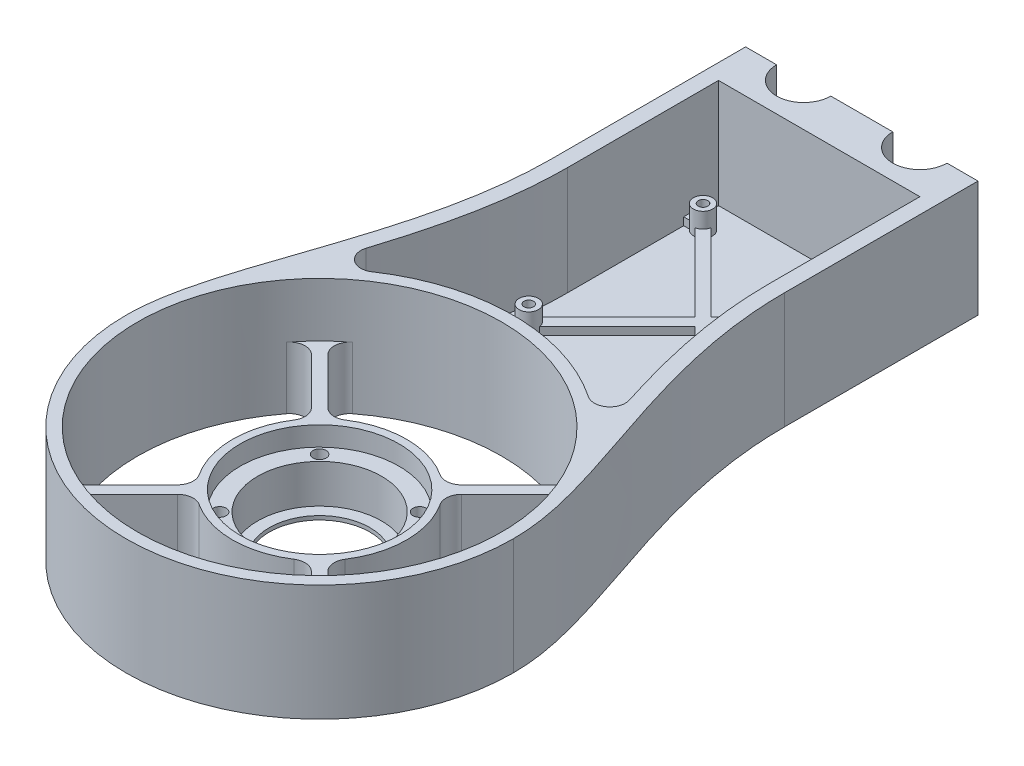
SolidWorks part; units mm, degrees
material "3.1355 (EN-AW 2024)"
ref_plane "Front" through (0, 0, 0) normal (0, 0, 1) x (1, 0, 0)
ref_plane "Top" through (0, 0, 0) normal (0, 1, 0) x (1, 0, 0)
ref_plane "Right" through (0, 0, 0) normal (1, 0, 0) x (0, 0, -1)
sketch "Эскиз1" plane through (0, 0, 0) normal (0, 1, 0) x (1, 0, 0)
  line L0 (0, 0) -> (8, 0)
  line L1 (0, 0) -> (0, -100) construction
  line L2 (0, -12.5175) -> (60, -12.5175) construction
  line L3 (8, 0) -> (22, 0) construction
  line L4 (30, -12.5175) -> (30, 0) construction
  line L5 (60, 0) -> (52, 0)
  line L6 (60, 0) -> (60, -100) construction
  line L7 (22, 0) -> (38, 0)
  line L8 (30, 0) -> (30, -140) construction
  line L9 (0, -80.7644) -> (0, -19.2352) construction
  line L10 (0, 0) -> (0, -50)
  line L11 (60, 0) -> (60, -50)
  arc A0 (22, 0) -> (8, 0) centre (15, 0) cw
  arc A1 (38, 0) -> (52, 0) centre (45, 0) ccw
  circle A2 centre (30, -140) radius 47 construction
  circle A3 centre (30, -140) radius 50 construction
  arc A4 (-20, -140) -> (80, -140) centre (30, -140) ccw
  spline S0 degree 3 poles (0, -50) (0, -86.1164) (-20.1607, -116.6426) (-20, -140) knots 0 0 0 0 1 1 1 1
  spline S1 degree 3 poles (60, -50) (60, -86.1164) (80.1607, -116.6426) (80, -140) knots 0 0 0 0 1 1 1 1
  dimension "D3" = 7
  dimension "D5" = 94
  dimension "D6" = 100
  dimension "D1" = 60
  dimension "D2" = 8
  dimension "D4" = 140
extrude "Бобышка-Вытянуть1" add sketch "Эскиз1" along normal blind 30
sketch "Эскиз2" plane through (0, 0, 0) normal (0, -1, 0) x (1, 0, 0)
  line L10 (3, 50) -> (3, 3)
  line L11 (3, 3) -> (5.4606, 3)
  line L12 (24.5394, 3) -> (35.4606, 3)
  line L13 (54.5394, 3) -> (57, 3)
  line L14 (57, 3) -> (57, 50)
  line L15 (0, 50) -> (0, 0)
  line L16 (60, 0) -> (60, 50)
  line L17 (52, 0) -> (60, 0)
  line L18 (22, 0) -> (38, 0)
  line L19 (0, 0) -> (8, 0)
  line L20 (0, 50) -> (0, 0) construction
  line L21 (60, 0) -> (60, 50) construction
  line L22 (52, 0) -> (60, 0) construction
  line L23 (22, 0) -> (38, 0) construction
  line L24 (0, 0) -> (8, 0) construction
  arc A6 (24.5394, 3) -> (5.4606, 3) centre (15, 0) ccw
  arc A7 (54.5394, 3) -> (35.4606, 3) centre (45, 0) ccw
  arc A8 (77, 139.9896) -> (-17, 139.9896) centre (30, 140) ccw
  arc A9 (80, 140) -> (-20, 140) centre (30, 140) ccw
  arc A10 (52, 0) -> (38, 0) centre (45, 0) ccw
  arc A11 (22, 0) -> (8, 0) centre (15, 0) ccw
  arc A12 (80, 140) -> (-20, 140) centre (30, 140) ccw construction
  arc A13 (52, 0) -> (38, 0) centre (45, 0) ccw construction
  arc A14 (22, 0) -> (8, 0) centre (15, 0) ccw construction
  spline S4 degree 1 poles (57, 50) (77, 139.9896) knots 0 0 1 1 construction
  spline S5 degree 1 poles (-17, 139.9896) (3, 50) knots 0 0 1 1 construction
  spline S6 degree 3 poles (1977.4891, 89.0603) (-2125.3468, 381.0882) (2082.0698, -1.9555) (-1932.4354, -415.3328) knots -3.22742 -3.22742 -3.22742 -3.22742 4.19175 4.19175 4.19175 4.19175 only from (-20, 140) to (0, 50)
  spline S7 degree 3 poles (1992.5098, -415.3405) (-2022.1214, -1.9603) (2185.3713, 381.0899) (-1917.4879, 89.0604) knots -3.191796 -3.191796 -3.191796 -3.191796 4.227419 4.227419 4.227419 4.227419 only from (60, 50) to (80, 140)
  spline S8 degree 3 poles (-20, 140) (-20.1607, 116.6426) (0, 86.1164) (0, 50) knots 0 0 0 0 1 1 1 1 construction
  spline S9 degree 3 poles (60, 50) (60, 86.1164) (80.1607, 116.6426) (80, 140) knots 0 0 0 0 1 1 1 1 construction
  spline S10 degree 3 poles (57, 50) (57, 51.1576) (57.0406, 53.4814) (57.2737, 58.0563) (57.8301, 63.6858) (58.8583, 70.2789) (60.6259, 78.8547) (63.4225, 89.1628) (67.2235, 100.8568) (70.9828, 111.8512) (73.6804, 120.3995) (75.3444, 126.839) (76.2902, 131.4603) (76.7834, 135.1232) (76.9778, 137.9484) (77.0049, 139.3044) (77, 139.9896) knots 0 0 0 0 0.031255 0.06251 0.12502 0.18753 0.25004 0.375059 0.500079 0.625099 0.750119 0.812629 0.875139 0.937649 0.968904 1.000159 1.000159 1.000159 1.000159
  spline S11 degree 3 poles (-17, 139.9896) (-17.0049, 139.3044) (-16.9778, 137.9484) (-16.7834, 135.1232) (-16.2902, 131.4603) (-15.3444, 126.839) (-13.6804, 120.3995) (-10.9828, 111.8512) (-7.2235, 100.8568) (-3.4225, 89.1628) (-0.6259, 78.8547) (1.1417, 70.2789) (2.1699, 63.6858) (2.7263, 58.0563) (2.9594, 53.4814) (3, 51.1576) (3, 50) knots -0.000159 -0.000159 -0.000159 -0.000159 0.031096 0.062351 0.124861 0.187371 0.249881 0.374901 0.499921 0.624941 0.74996 0.81247 0.87498 0.93749 0.968745 1 1 1 1
  dimension "D1" = 0
  dimension "D2" = 3
extrude "Вырез-Вытянуть1" cut sketch "Эскиз2" against normal through all
sketch "Эскиз3" plane through (0, 0, 0) normal (0, -1, 0) x (1, 0, 0)
  circle A0 centre (30, 140) radius 13
  circle A1 centre (30, 140) radius 22.5
  dimension "D1" = 26
  dimension "D2" = 45
extrude "Бобышка-Вытянуть2" add sketch "Эскиз3" against normal blind 16 separate body
sketch "Эскиз4" plane through (0, 16, 0) normal (0, 1, 0) x (1, 0, 0)
  circle A2 centre (30, -140) radius 20.5
  dimension "D1" = 41
extrude "Вырез-Вытянуть2" cut sketch "Эскиз4" against normal blind 5
sketch "Эскиз5" plane through (0, 11, 0) normal (0, 1, 0) x (1, 0, 0)
  circle A0 centre (30, -140) radius 16
  dimension "D1" = 32
extrude "Вырез-Вытянуть3" cut sketch "Эскиз5" against normal blind 10
sketch "Эскиз6" plane through (0, 11, 0) normal (0, 1, 0) x (1, 0, 0)
  line L0 (30, -140) -> (11.75, -140) construction
  line L1 (30, -140) -> (17.0953, -127.0953) construction
  line L2 (30, -140) -> (42.9047, -127.0953) construction
  line L3 (30, -140) -> (42.9047, -152.9047) construction
  line L4 (30, -140) -> (17.0953, -152.9047) construction
  circle A0 centre (30, -140) radius 18.25 construction
  point P11 (30, -140)
  dimension "D1" = 36.5
  dimension "D2" = 45
  dimension "D3" = 4
hole_wizard "Отверстие с зазором M31" positions "Эскиз8" profile "Эскиз7" hole size "M3" standard "Ansi Metric" end condition through all
sketch "Эскиз8" plane through (0, 11, 0) normal (0, 1, 0) x (1, 0, 0)
  point P0 (17.0953, -127.0953)
  point P3 (42.9047, -127.0953)
  point P6 (42.9047, -152.9047)
  point P9 (17.0953, -152.9047)
sketch "Эскиз7" plane through (17.0953, 11, 127.0953) normal (1, 0, 0) x (0, 0, 1)
  line L0 (0, 0) -> (0, 11)
  line L1 (0, 11) -> (1.7, 11)
  line L2 (1.7, 11) -> (1.7, 0)
  line L5 (1.7, 0) -> (0, 0)
  line L11 (0, -6.35) -> (0, 107.95) construction
  dimension "Диаметр сквозного отверстия" = 3.4
  dimension "Глубина сквозного отверстия" = 11
sketch "Эскиз9" plane through (0, 0, 0) normal (0, -1, 0) x (1, 0, 0)
  arc A0 (-10.5903, 110.8036) -> (70.5903, 110.8036) centre (30, 140) ccw
  arc A2 (-17, 139.9896) -> (77, 139.9896) centre (30, 140) ccw
  spline S1 degree 3 poles (91.2044, 1134.1092) (3.1868, 169.3541) (-18.6659, 162.4892) (-16.7834, 135.1232) (-16.2902, 131.4603) (-15.3444, 126.839) (-13.6804, 120.3995) (-10.9828, 111.8512) (-7.2235, 100.8568) (-3.4225, 89.1628) (-0.6259, 78.8547) (1.1417, 70.2789) (2.1699, 63.6858) (2.7263, 58.0563) (5.494, 3.7367) (-31.1495, -67.1177) (-220.6475, 1024.6502) knots -1.086154 -1.086154 -1.086154 -1.086154 0.031096 0.062351 0.124861 0.187371 0.249881 0.374901 0.499921 0.624941 0.74996 0.81247 0.87498 0.93749 0.968745 2.359394 2.359394 2.359394 2.359394 only from (-17, 139.9896) to (3, 50) construction
  spline S2 degree 3 poles (280.6492, 1024.66) (91.1497, -67.1181) (54.506, 3.7366) (57.2737, 58.0563) (57.8301, 63.6858) (58.8583, 70.2789) (60.6259, 78.8547) (63.4225, 89.1628) (67.2235, 100.8568) (70.9828, 111.8512) (73.6804, 120.3995) (75.3444, 126.839) (76.2902, 131.4603) (76.7834, 135.1232) (78.6659, 162.4891) (56.8135, 169.354) (-31.2029, 1134.0935) knots -1.359398 -1.359398 -1.359398 -1.359398 0.031255 0.06251 0.12502 0.18753 0.25004 0.375059 0.500079 0.625099 0.750119 0.812629 0.875139 0.937649 0.968904 2.086148 2.086148 2.086148 2.086148 only from (57, 50) to (77, 139.9896) construction
  spline S3 degree 3 poles (70.5903, 110.8036) (70.6927, 111.1128) (71.9682, 114.9738) (73.6804, 120.3995) (75.3444, 126.839) (76.2902, 131.4603) (76.7834, 135.1232) (76.9778, 137.9484) (77.0049, 139.3044) (77, 139.9896) knots 0.614251 0.614251 0.614251 0.614251 0.625099 0.750119 0.812629 0.875139 0.937649 0.968904 1.000159 1.000159 1.000159 1.000159
  spline S4 degree 3 poles (-17, 139.9896) (-17.0049, 139.3044) (-16.9778, 137.9484) (-16.7834, 135.1232) (-16.2902, 131.4603) (-15.3444, 126.839) (-13.6804, 120.3995) (-11.9682, 114.9738) (-10.6927, 111.1128) (-10.5903, 110.8036) knots -0.000159 -0.000159 -0.000159 -0.000159 0.031096 0.062351 0.124861 0.187371 0.249881 0.374901 0.385749 0.385749 0.385749 0.385749
extrude "Бобышка-Вытянуть3" add sketch "Эскиз9" against normal up to surface (16 mm away) up to face at (30, 16, 160.5)
sketch "Эскиз10" plane through (0, 0, 0) normal (0, -1, 0) x (1, 0, 0)
  line L0 (30, 140) -> (-3.2267, 106.7587) construction
  line L1 (30, 140) -> (-17, 139.9896) construction
  line L2 (13.0616, 154.8101) -> (-4.2848, 172.1489)
  line L3 (15.1899, 123.0616) -> (-2.1489, 105.7152)
  line L4 (13.068, 125.1825) -> (-4.2708, 107.8362)
  line L5 (31.0609, 138.9396) -> (-2.1658, 105.6982) construction
  line L6 (15.1825, 156.932) -> (-2.1638, 174.2708)
  line L7 (44.8101, 156.9384) -> (62.1489, 174.2848)
  line L8 (46.932, 154.8175) -> (64.2708, 172.1638)
  line L9 (46.9384, 125.1899) -> (64.2848, 107.8511)
  line L10 (44.8175, 123.068) -> (62.1638, 105.7292)
  circle A0 centre (30, 140) radius 22.5 construction
  arc A1 (13.068, 125.1825) -> (15.1899, 123.0616) centre (30, 140) ccw
  circle A2 centre (30, 140) radius 47 construction
  arc A3 (-4.2708, 107.8362) -> (-2.1489, 105.7152) centre (30, 140) ccw
  arc A4 (-2.1638, 174.2708) -> (-4.2848, 172.1489) centre (30, 140) ccw
  arc A5 (15.1825, 156.932) -> (13.0616, 154.8101) centre (30, 140) ccw
  arc A6 (64.2708, 172.1638) -> (62.1489, 174.2848) centre (30, 140) ccw
  arc A7 (46.932, 154.8175) -> (44.8101, 156.9384) centre (30, 140) ccw
  arc A8 (62.1638, 105.7292) -> (64.2848, 107.8511) centre (30, 140) ccw
  arc A9 (44.8175, 123.068) -> (46.9384, 125.1899) centre (30, 140) ccw
  point P5 (28.9391, 141.0604)
  point P9 (-4.2877, 107.8192)
  point P29 (30, 140)
  point P36 (30, 140)
  dimension "D1" = 45
  dimension "D2" = 4
  dimension "D3" = 1.5
extrude "Бобышка-Вытянуть4" add sketch "Эскиз10" against normal up to surface (16 mm away) up to face at (30, 16, 160.5)
fillet "Скругление1" radius 4 2 edges
fillet "Скругление2" radius 4 16 edges at (13.068, 8, 125.1825) (-4.2708, 8, 107.8362) (13.0616, 8, 154.8101) (-4.2848, 8, 172.1489) (-2.1638, 8, 174.2708) (15.1825, 8, 156.932) (44.8101, 8, 156.9384) (62.1489, 8, 174.2848) (46.932, 8, 154.8175) (64.2708, 8, 172.1638) (46.9384, 8, 125.1899) (64.2848, 8, 107.8511) (44.8175, 8, 123.068) (15.1899, 8, 123.0616) (-2.1489, 8, 105.7152) (62.1638, 8, 105.7292)
sketch "Эскиз11" plane through (0, 30, 0) normal (0, 1, 0) x (1, 0, 0)
  line L0 (3, -50) -> (3, -3) construction
  line L1 (3, -10) -> (57, -10)
  line L2 (57, -3) -> (57, -50) construction
  line L3 (54.5394, -3) -> (57, -3) construction
  line L4 (24.5394, -3) -> (35.4606, -3) construction
  line L5 (3, -3) -> (5.4606, -3) construction
  line L6 (54.5394, -3) -> (57, -3)
  line L7 (24.5394, -3) -> (35.4606, -3)
  line L8 (3, -3) -> (5.4606, -3)
  line L9 (3, -10) -> (3, -3)
  line L10 (57, -3) -> (57, -10)
  arc A0 (5.4606, -3) -> (24.5394, -3) centre (15, 0) ccw construction
  arc A1 (5.4606, -3) -> (24.5394, -3) centre (15, 0) ccw
  arc A2 (35.4606, -3) -> (54.5394, -3) centre (45, 0) ccw construction
  arc A3 (35.4606, -3) -> (54.5394, -3) centre (45, 0) ccw
  line M2 (3, -50) -> (3, -3)
  line M3 (3, -3) -> (5.4606, -3)
  arc M4 (5.4606, -3) -> (24.5394, -3) centre (15, 0) ccw
  line M5 (24.5394, -3) -> (35.4606, -3)
  arc M6 (35.4606, -3) -> (54.5394, -3) centre (45, 0) ccw
  line M7 (54.5394, -3) -> (57, -3)
  line M8 (57, -3) -> (57, -50)
extrude "Бобышка-Вытянуть5" add sketch "Эскиз11" against normal through all contours L1 M4 M6 M5 | L1 M6 M8 M7 | L1 M2 M4 M3 region at (5.9677, 30, 7.3317) region at (54.0323, 30, 7.3317) region at (30, 30, 7.0198)
sketch "Эскиз12" plane through (0, 16, 0) normal (0, 1, 0) x (1, 0, 0)
  arc A0 (59.1694, -99.3903) -> (0.8306, -99.3903) centre (30, -140) ccw construction
  arc A1 (-5.3129, -94.9233) -> (0.8306, -99.3903) centre (-1.5029, -96.1415) ccw construction
  arc A2 (59.1694, -99.3903) -> (65.3129, -94.9233) centre (61.5029, -96.1415) ccw construction
  arc A3 (59.1694, -99.3903) -> (0.8306, -99.3903) centre (30, -140) ccw
  arc A4 (-5.3129, -94.9233) -> (0.8306, -99.3903) centre (-1.5029, -96.1415) ccw
  arc A5 (59.1694, -99.3903) -> (65.3129, -94.9233) centre (61.5029, -96.1415) ccw
  arc A7 (58.7182, -102.7943) -> (1.298, -102.7818) centre (30, -140) ccw construction
  arc A8 (77, -139.9896) -> (-17, -139.9896) centre (30, -140) ccw
  spline S0 degree 3 poles (-1914.7367, 431.9839) (72.5207, 220.6611) (28.2156, 2.7872) (-10.9828, -111.8512) (-13.6804, -120.3995) (-15.3444, -126.839) (-16.2902, -131.4603) (-16.7834, -135.1232) (-19.1296, -169.2301) (16.1331, -171.6324) (176.8285, -2130.3521) knots -3.597718 -3.597718 -3.597718 -3.597718 0.06297 0.187989 0.313009 0.375519 0.438029 0.500539 0.531794 1.947349 1.947349 1.947349 1.947349 only from (-5.3129, -94.9233) to (-17, -139.9896) construction
  spline S1 degree 3 poles (-5.3129, -94.9233) (-5.9422, -96.8917) (-7.8438, -102.671) (-10.9828, -111.8512) (-13.6804, -120.3995) (-15.3444, -126.839) (-16.2902, -131.4603) (-16.7834, -135.1232) (-16.9778, -137.9484) (-17.0049, -139.3044) (-17, -139.9896) knots -0.000159 -0.000159 -0.000159 -0.000159 0.06297 0.187989 0.313009 0.375519 0.438029 0.500539 0.531794 0.563049 0.563049 0.563049 0.563049
  spline S2 degree 3 poles (-116.8284, -2130.351) (43.8669, -171.6324) (79.1296, -169.2301) (76.7834, -135.1232) (76.2902, -131.4603) (75.3444, -126.839) (73.6804, -120.3995) (70.9828, -111.8512) (31.7842, 2.7877) (-12.5211, 220.6632) (1974.7671, 431.9871) knots -0.947348 -0.947348 -0.947348 -0.947348 0.468206 0.499461 0.561971 0.624481 0.686991 0.812011 0.93703 4.597736 4.597736 4.597736 4.597736 only from (77, -139.9896) to (65.3129, -94.9233) construction
  spline S3 degree 3 poles (77, -139.9896) (77.0049, -139.3044) (76.9778, -137.9484) (76.7834, -135.1232) (76.2902, -131.4603) (75.3444, -126.839) (73.6804, -120.3995) (70.9828, -111.8512) (67.8438, -102.671) (65.9422, -96.8917) (65.3129, -94.9233) knots 0.436951 0.436951 0.436951 0.436951 0.468206 0.499461 0.561971 0.624481 0.686991 0.812011 0.93703 1.000159 1.000159 1.000159 1.000159
extrude "Бобышка-Вытянуть6" add sketch "Эскиз12" along normal up to surface (14 mm away) up to face at (26.6667, 30, 74.4983)
sketch "Эскиз13" plane through (0, 30, 0) normal (0, 1, 0) x (1, 0, 0)
  line L3 (3, -50) -> (3, -10) construction
  line L4 (3, -10) -> (57, -10) construction
  line L5 (57, -10) -> (57, -50) construction
  line L6 (4, -50) -> (4, -11)
  line L7 (4, -11) -> (56, -11)
  line L8 (56, -11) -> (56, -50)
  line L9 (-4.3604, -95.2279) -> (-5.1661, -97.7479)
  line L10 (64.3604, -95.2279) -> (65.1661, -97.7479)
  line L12 (3, -50) -> (3, -10)
  line L13 (3, -10) -> (57, -10)
  line L14 (57, -10) -> (57, -50)
  arc A0 (-5.3129, -94.9233) -> (0.8306, -99.3903) centre (-1.5029, -96.1415) ccw construction
  arc A1 (-5.3129, -94.9233) -> (-5.1661, -97.7479) centre (-1.5029, -96.1415) ccw
  arc A2 (59.1694, -99.3903) -> (65.3129, -94.9233) centre (61.5029, -96.1415) ccw construction
  arc A4 (65.1661, -97.7479) -> (65.3129, -94.9233) centre (61.5029, -96.1415) ccw
  spline S2 degree 3 poles (1990.0869, -28.6531) (-145.5362, -228.9712) (-36.4686, -210.9677) (-0.6259, -78.8547) (1.1417, -70.2789) (2.1699, -63.6858) (2.7263, -58.0563) (6.1081, 8.3156) (-50.2334, 100.952) (-382.6884, -2011.4141) knots -3.1933 -3.1933 -3.1933 -3.1933 0.624941 0.74996 0.81247 0.87498 0.93749 0.968745 2.688753 2.688753 2.688753 2.688753 only from (-5.3129, -94.9233) to (3, -50) construction
  spline S3 degree 3 poles (442.6888, -2011.4164) (110.2335, 100.952) (53.8919, 8.3156) (57.2737, -58.0563) (57.8301, -63.6858) (58.8583, -70.2789) (60.6259, -78.8547) (96.4685, -210.9671) (205.5353, -228.971) (-1930.0571, -28.6559) knots -1.688754 -1.688754 -1.688754 -1.688754 0.031255 0.06251 0.12502 0.18753 0.25004 0.375059 4.193282 4.193282 4.193282 4.193282 only from (57, -50) to (65.3129, -94.9233) construction
  spline S4 degree 1 poles (-4.3604, -95.2279) (4, -50) knots 0 0 1 1 construction
  spline S5 degree 1 poles (56, -50) (64.3604, -95.2279) knots 0 0 1 1 construction
  spline S6 degree 3 poles (-4.3604, -95.2279) (-3.8086, -93.502) (-2.7375, -90.0676) (-0.6784, -82.9518) (1.5892, -73.7478) (3.1808, -64.0885) (3.8747, -56.1319) (4, -52.035) (4, -50) knots 0.563049 0.563049 0.563049 0.563049 0.617668 0.672287 0.781524 0.890762 0.945381 1 1 1 1
  spline S7 degree 3 poles (56, -50) (56, -52.035) (56.1253, -56.1319) (56.8192, -64.0885) (58.4108, -73.7478) (60.6784, -82.9518) (62.7375, -90.0676) (63.8086, -93.502) (64.3604, -95.2279) knots 0 0 0 0 0.054619 0.109238 0.218476 0.327713 0.382332 0.436951 0.436951 0.436951 0.436951
  spline S8 degree 3 poles (-5.3129, -94.9233) (-4.6959, -92.9935) (-2.8576, -87.0808) (-0.6259, -78.8547) (1.1417, -70.2789) (2.1699, -63.6858) (2.7263, -58.0563) (2.9594, -53.4814) (3, -51.1576) (3, -50) knots 0.563049 0.563049 0.563049 0.563049 0.624941 0.74996 0.81247 0.87498 0.93749 0.968745 1 1 1 1
  spline S9 degree 3 poles (57, -50) (57, -51.1576) (57.0406, -53.4814) (57.2737, -58.0563) (57.8301, -63.6858) (58.8583, -70.2789) (60.6259, -78.8547) (62.8576, -87.0808) (64.6959, -92.9935) (65.3129, -94.9233) knots 0 0 0 0 0.031255 0.06251 0.12502 0.18753 0.25004 0.375059 0.436951 0.436951 0.436951 0.436951
  dimension "D1" = 1
extrude "Бобышка-Вытянуть7" add sketch "Эскиз13" against normal up to surface (30 mm away) up to face at (25.3147, 0, 64.1334)
sketch "Эскиз14" plane through (0, 30, 0) normal (0, 1, 0) x (1, 0, 0)
  line L0 (4, -50) -> (56, -50)
  line L1 (-5.1661, -97.7479) -> (-4.3604, -95.2279) construction
  line L2 (-8.4599, -108.0495) -> (-4.3604, -95.2279)
  line L3 (64.3604, -95.2279) -> (65.1661, -97.7479) construction
  line L4 (64.3604, -95.2279) -> (68.4599, -108.0495)
  arc A0 (59.1694, -99.3903) -> (0.8306, -99.3903) centre (30, -140) ccw construction
  arc A1 (68.4599, -108.0495) -> (-8.4599, -108.0495) centre (30, -140) ccw
  spline S1 degree 3 poles (-385.17, -2058.4209) (-54.6447, -176.3295) (-20.9375, -152.9616) (-0.6784, -82.9518) (1.5892, -73.7478) (3.1808, -64.0885) (10.1833, 16.2006) (-64.7343, 136.1761) (-591.1703, -1957.0915) knots -1.367986 -1.367986 -1.367986 -1.367986 0.617668 0.672287 0.781524 0.890762 0.945381 2.986145 2.986145 2.986145 2.986145 only from (-4.3604, -95.2279) to (4, -50) construction
  spline S3 degree 3 poles (-4.3604, -95.2279) (-3.8086, -93.502) (-2.7375, -90.0676) (-0.6784, -82.9518) (1.5892, -73.7478) (3.1808, -64.0885) (3.8747, -56.1319) (4, -52.035) (4, -50) knots 0.563049 0.563049 0.563049 0.563049 0.617668 0.672287 0.781524 0.890762 0.945381 1 1 1 1
  spline S4 degree 3 poles (651.1712, -1957.0948) (124.7344, 136.1762) (49.8167, 16.2006) (56.8192, -64.0885) (58.4108, -73.7478) (60.6784, -82.9518) (80.9375, -152.9615) (114.6445, -176.3294) (445.1676, -2058.4071) knots -1.986146 -1.986146 -1.986146 -1.986146 0.054619 0.109238 0.218476 0.327713 0.382332 2.367981 2.367981 2.367981 2.367981 only from (56, -50) to (64.3604, -95.2279) construction
  spline S5 degree 3 poles (56, -50) (56, -52.035) (56.1253, -56.1319) (56.8192, -64.0885) (58.4108, -73.7478) (60.6784, -82.9518) (62.7375, -90.0676) (63.8086, -93.502) (64.3604, -95.2279) knots 0 0 0 0 0.054619 0.109238 0.218476 0.327713 0.382332 0.436951 0.436951 0.436951 0.436951
extrude "Вырез-Вытянуть4" cut sketch "Эскиз14" against normal through all
sketch "Эскиз15" plane through (0, 30, 0) normal (0, 1, 0) x (1, 0, 0)
  line L0 (-8.4599, -108.0495) -> (-4.3604, -95.2279) construction
  line L1 (-8.4599, -108.0495) -> (-4.3604, -95.2279)
  line L2 (64.3604, -95.2279) -> (68.4599, -108.0495) construction
  line L3 (64.3604, -95.2279) -> (68.4599, -108.0495)
  arc A1 (68.4599, -108.0495) -> (-8.4599, -108.0495) centre (30, -140) ccw construction
  arc A2 (2.0776, -98.523) -> (-3.9825, -94.039) centre (-0.1562, -95.2048) cw
  arc A3 (63.9825, -94.0392) -> (57.9224, -98.523) centre (60.1562, -95.2048) cw
  arc A4 (68.4599, -108.0495) -> (57.9224, -98.523) centre (30, -140) ccw
  arc A5 (2.0776, -98.523) -> (-8.4599, -108.0495) centre (30, -140) ccw
  spline S0 degree 3 poles (-385.17, -2058.4209) (-54.6447, -176.3295) (-20.9375, -152.9616) (-0.6784, -82.9518) (1.5892, -73.7478) (3.1808, -64.0885) (10.1833, 16.2006) (-64.7343, 136.1761) (-591.1703, -1957.0915) knots -1.367986 -1.367986 -1.367986 -1.367986 0.617668 0.672287 0.781524 0.890762 0.945381 2.986145 2.986145 2.986145 2.986145 only from (-4.3604, -95.2279) to (4, -50) construction
  spline S2 degree 3 poles (-4.3604, -95.2279) (-4.2336, -94.8313) (-4.1077, -94.4352) (-3.9825, -94.039) knots 0.563049 0.563049 0.563049 0.563049 0.575599 0.575599 0.575599 0.575599
  spline S3 degree 3 poles (651.1712, -1957.0948) (124.7344, 136.1762) (49.8167, 16.2006) (56.8192, -64.0885) (58.4108, -73.7478) (60.6784, -82.9518) (80.9375, -152.9615) (114.6445, -176.3294) (445.1676, -2058.4071) knots -1.986146 -1.986146 -1.986146 -1.986146 0.054619 0.109238 0.218476 0.327713 0.382332 2.367981 2.367981 2.367981 2.367981 only from (56, -50) to (64.3604, -95.2279) construction
  spline S4 degree 3 poles (63.9825, -94.0392) (64.1077, -94.4353) (64.2336, -94.8313) (64.3604, -95.2279) knots 0.424402 0.424402 0.424402 0.424402 0.436951 0.436951 0.436951 0.436951
  arc M12 (68.4599, -108.0495) -> (-8.4599, -108.0495) centre (30, -140) ccw
  dimension "D1" = 4
  dimension "D2" = 4
extrude "Бобышка-Вытянуть9" add sketch "Эскиз15" against normal blind 30 contours A2 M12 | A3 M12 region at (64.2901, 30, 101.1221) region at (-4.2901, 30, 101.1221)
sketch "Эскиз16" plane through (0, 0, 0) normal (0, -1, 0) x (1, 0, 0)
  line L6 (-7.8525, 101.9352) -> (-2.0682, 81.4275)
  line L7 (-2.0682, 81.4275) -> (2.4014, 58.8164)
  line L8 (2.4014, 58.8164) -> (2.4014, 39.0974)
  line L9 (2.4014, 39.0974) -> (2.4014, 22.5335)
  line L10 (2.4014, 22.5335) -> (2.4014, 9.3875)
  line L11 (2.4014, 9.3875) -> (57.3515, 9.3875)
  line L12 (57.3515, 9.3875) -> (57.3515, 36.7312)
  line L13 (57.3515, 36.7312) -> (57.3515, 56.976)
  line L14 (57.3515, 56.976) -> (62.6099, 81.4275)
  line L15 (62.6099, 81.4275) -> (67.0202, 101.9352)
  line L16 (67.0202, 101.9352) -> (62.6099, 101.9352)
  line L17 (62.6099, 101.9352) -> (57.3515, 100.8957)
  line L18 (57.3515, 100.8957) -> (53.1046, 97.8523)
  line L19 (53.1046, 97.8523) -> (47.4934, 95.4064)
  line L20 (47.4934, 95.4064) -> (40.9286, 92.5448)
  line L21 (40.9286, 92.5448) -> (34.9313, 92.5448)
  line L22 (34.9313, 92.5448) -> (28.8409, 91.3409)
  line L23 (28.8409, 91.3409) -> (21.7336, 92.8693)
  line L24 (21.7336, 92.8693) -> (13.4158, 94.6581)
  line L25 (13.4158, 94.6581) -> (5.0927, 97.8523)
  line L26 (5.0927, 97.8523) -> (-1.0469, 101.9352)
  line L27 (-1.0469, 101.9352) -> (-7.8525, 101.9352)
extrude "Бобышка-Вытянуть10" add sketch "Эскиз16" against normal blind 2
sketch "Эскиз17" plane through (0, 11, 0) normal (0, 1, 0) x (1, 0, 0)
  circle A0 centre (30, -140) radius 18.25 construction
  point P4 (30, -121.75)
  point P5 (42.9047, -127.0953)
  point P8 (48.25, -140)
  point P9 (42.9047, -152.9047)
  point P10 (30, -158.25)
  point P11 (17.0953, -152.9047)
  point P12 (11.75, -140)
  point P13 (17.0953, -127.0953)
  point P14 (30, -140)
  dimension "D1" = 8
sketch "Эскиз18" plane through (0, 2, 0) normal (0, 1, 0) x (1, 0, 0)
  line L0 (5, -16) -> (55, -16)
  line L1 (7.5, -18.5) -> (52.5, -18.5) construction
  line L2 (7.5, -18.5) -> (7.5, -63.5) construction
  line L3 (7.5, -63.5) -> (52.5, -63.5) construction
  line L4 (52.5, -18.5) -> (52.5, -63.5) construction
  line L5 (55, -16) -> (55, -66)
  line L6 (5, -66) -> (55, -66)
  line L7 (5, -16) -> (5, -66)
  line L10 (4, -50) -> (4, -11) construction
  line L11 (4, -11) -> (56, -11) construction
  circle A0 centre (7.5, -18.5) radius 1.5
  circle A1 centre (52.5, -18.5) radius 1.5
  circle A2 centre (7.5, -63.5) radius 1.5
  circle A3 centre (52.5, -63.5) radius 1.5
  dimension "D4" = 3
  dimension "D1" = 45
  dimension "D3" = 1
  dimension "D5" = 5
  dimension "D2" = 2.5
sketch "Эскиз19" plane through (0, 2, 0) normal (0, 1, 0) x (1, 0, 0)
  circle A0 centre (7.5, -18.5) radius 2.5
  circle A1 centre (52.5, -18.5) radius 2.5
  circle A2 centre (52.5, -63.5) radius 2.5
  circle A3 centre (7.5, -63.5) radius 2.5
  dimension "D1" = 5
extrude "Бобышка-Вытянуть11" add sketch "Эскиз19" along normal blind 6
hole_wizard "Отверстие обработанное метчиком M3x0.51" positions "Эскиз21" profile "Эскиз20" tap size "M3x0.5" standard "Ansi Metric"
sketch "Эскиз21" plane through (0, 8, 0) normal (0, 1, 0) x (1, 0, 0)
  point P0 (7.5, -18.5)
  point P3 (52.5, -18.5)
  point P6 (52.5, -63.5)
  point P9 (7.5, -63.5)
sketch "Эскиз20" plane through (7.5, 8, 18.5) normal (1, 0, 0) x (0, 0, 1)
  line L0 (0, 0) -> (0, 6.7511)
  line L1 (0, 6.7511) -> (1.25, 6)
  line L2 (1.25, 6) -> (1.25, 0)
  line L5 (1.25, 0) -> (0, 0)
  line L10 (0, 6.7511) -> (-1.25, 6) construction
  line L11 (0, -6.35) -> (0, 107.95) construction
  dimension "Диаметр сверла" = 2.5
  dimension "Глубина сверла" = 6
  dimension "Угол заточки сверла" = 118
cosmetic thread "Отверстие резьбы1" parameters "D1"=6, "D2"=3
cosmetic thread "Отверстие резьбы2" parameters "D1"=6, "D2"=3
cosmetic thread "Отверстие резьбы3" parameters "D1"=6, "D2"=3
cosmetic thread "Отверстие резьбы4" parameters "D1"=6, "D2"=3
sketch "Эскиз22" plane through (0, 2, 0) normal (0, 1, 0) x (1, 0, 0)
  line L0 (9.2678, -61.7322) -> (50.7322, -20.2678) construction
  line L1 (9.2678, -20.2678) -> (50.7322, -61.7322) construction
  line L2 (7.8536, -20.9749) -> (27.8787, -41)
  line L3 (9.9749, -63.1464) -> (30, -43.1213)
  line L4 (9.9749, -18.8536) -> (30, -38.8787)
  line L5 (7.8536, -61.0251) -> (27.8787, -41)
  line L6 (32.1213, -41) -> (52.1464, -61.0251)
  line L7 (30, -38.8787) -> (50.0251, -18.8536)
  line L8 (10.3284, -19.2071) -> (51.7929, -60.6716) construction
  line L9 (30, -43.1213) -> (50.0251, -63.1464)
  line L10 (8.2071, -60.6716) -> (49.6716, -19.2071) construction
  line L11 (32.1213, -41) -> (52.1464, -20.9749)
  line L12 (8.2071, -21.3284) -> (49.6716, -62.7929) construction
  line L13 (5, -63.5) -> (3.1375, -63.5) construction
  line L14 (10.3284, -62.7929) -> (51.7929, -21.3284) construction
  line L15 (5, -18.5) -> (4, -18.5) construction
  line L16 (4, -50) -> (4, -11) construction
  line L17 (55, -18.5) -> (56, -18.5) construction
  line L18 (56, -11) -> (56, -50) construction
  line L19 (55, -63.5) -> (56.8625, -63.5) construction
  line L20 (5.5, -17) -> (4, -17)
  line L21 (54.5, -20) -> (56, -20)
  line L22 (54.5, -65) -> (57.0591, -65)
  line L23 (5.5, -62) -> (3.315, -62)
  line L24 (5.5, -20) -> (4, -20)
  line L25 (54.5, -17) -> (56, -17)
  line L26 (54.5, -62) -> (56.685, -62)
  line L27 (5.5, -65) -> (2.9409, -65)
  line L28 (5, -65) -> (3.1375, -65) construction
  line L29 (5, -62) -> (3.1375, -62) construction
  line L30 (4, -20) -> (4, -17)
  line L31 (5, -17) -> (4, -17) construction
  line L32 (5, -20) -> (4, -20) construction
  line L33 (56, -11) -> (56, -50) construction
  line L34 (56, -17) -> (56, -20)
  line L35 (55, -17) -> (56, -17) construction
  line L36 (55, -20) -> (56, -20) construction
  line L37 (55, -65) -> (56.8625, -65) construction
  line L38 (55, -62) -> (56.8625, -62) construction
  line L39 (7.5, -63.5) -> (52.5, -63.5) construction
  line L40 (7.5, -63.5) -> (52.5, -63.5)
  arc A1 (7.8536, -20.9749) -> (9.9749, -18.8536) centre (7.5, -18.5) ccw
  arc A3 (54.5, -20) -> (54.5, -17) centre (52.5, -18.5) ccw
  arc A5 (54.5, -65) -> (54.5, -62) centre (52.5, -63.5) ccw
  arc A7 (10, -63.5) -> (7.8536, -61.0251) centre (7.5, -63.5) ccw
  circle A8 centre (7.5, -18.5) radius 2.5
  circle A9 centre (52.5, -18.5) radius 2.5
  circle A10 centre (52.5, -63.5) radius 2.5
  arc A11 (5.5, -17) -> (5.5, -20) centre (7.5, -18.5) ccw
  arc A12 (50.0251, -18.8536) -> (52.1464, -20.9749) centre (52.5, -18.5) ccw
  arc A13 (52.1464, -61.0251) -> (50, -63.5) centre (52.5, -63.5) ccw
  circle A14 centre (7.5, -63.5) radius 2.5
  arc A15 (5.5, -62) -> (5.5, -65) centre (7.5, -63.5) ccw
  spline S0 degree 3 poles (-3.9825, -94.039) (-3.563, -92.7112) (-2.6192, -89.6589) (-0.6784, -82.9518) (1.5892, -73.7478) (3.1808, -64.0885) (3.8747, -56.1319) (4, -52.035) (4, -50) knots 0.575599 0.575599 0.575599 0.575599 0.617668 0.672287 0.781524 0.890762 0.945381 1 1 1 1 construction
  spline S1 degree 3 poles (651.1606, -1957.0528) (124.7334, 136.1746) (49.8167, 16.2002) (56.8192, -64.0885) (58.4108, -73.7478) (60.6784, -82.9518) (80.9333, -152.9469) (114.6297, -176.3191) (444.9434, -2057.1308) knots -1.986132 -1.986132 -1.986132 -1.986132 0.054619 0.109238 0.218476 0.327713 0.382332 2.367532 2.367532 2.367532 2.367532 only from (56, -50) to (63.9825, -94.0392) construction
  spline S2 degree 3 poles (-384.9424, -2057.1249) (-54.6296, -176.319) (-20.9332, -152.9468) (-0.6784, -82.9518) (1.5892, -73.7478) (3.1808, -64.0885) (10.1832, 16.1998) (-64.7327, 136.1735) (-591.1528, -1957.0216) knots -1.36753 -1.36753 -1.36753 -1.36753 0.617668 0.672287 0.781524 0.890762 0.945381 2.986122 2.986122 2.986122 2.986122 only from (-3.9825, -94.039) to (4, -50) construction
  spline S3 degree 3 poles (2.9409, -65) (3.0739, -64.0316) (3.1992, -63.0317) (3.312, -62.0268) (3.315, -62) knots 0.863647 0.863647 0.863647 0.863647 0.890762 0.891504 0.891504 0.891504 0.891504
  spline S4 degree 3 poles (56.685, -62) (56.688, -62.0268) (56.8008, -63.0317) (56.9261, -64.0316) (57.0591, -65) knots 0.108496 0.108496 0.108496 0.108496 0.109238 0.136353 0.136353 0.136353 0.136353
  circle M1 centre (52.5, -63.5) radius 2.5
  circle M2 centre (7.5, -18.5) radius 2.5
  spline M3 degree 3 poles (4, -50) (4, -52.035) (3.8747, -56.1319) (3.1808, -64.0885) (1.5892, -73.7478) (-0.6784, -82.9518) (-2.7375, -90.0676) (-3.8086, -93.502) (-4.3604, -95.2279) knots 0.563049 0.563049 0.563049 0.563049 0.617668 0.672287 0.781524 0.890762 0.945381 1 1 1 1 only from (4, -50) to (-3.9825, -94.039)
  spline M7 degree 3 poles (64.3604, -95.2279) (63.8086, -93.502) (62.7375, -90.0676) (60.6784, -82.9518) (58.4108, -73.7478) (56.8192, -64.0885) (56.1253, -56.1319) (56, -52.035) (56, -50) knots 0 0 0 0 0.054619 0.109238 0.218476 0.327713 0.382332 0.436951 0.436951 0.436951 0.436951 only from (63.9825, -94.0392) to (56, -50)
  line M8 (56, -50) -> (56, -11)
  line M10 (4, -11) -> (4, -50)
  circle M11 centre (52.5, -18.5) radius 2.5
  circle M12 centre (7.5, -63.5) radius 2.5
  dimension "D1" = 1.5
  dimension "D2" = 1.5
  dimension "D3" = 1.5
  dimension "D4" = 1.5
  dimension "D5" = 0
  dimension "D6" = 0
  dimension "D7" = 0
  dimension "D8" = 0
extrude "Бобышка-Вытянуть12" add sketch "Эскиз22" along normal blind 2 contours L6 L11 L7 L4 L2 L5 L3 L9 M11 M2 M12 M1 | L27 L23 M12 M3 | L24 L20 M2 M10 | L25 L21 M11 M8 | L26 L22 M1 M7 region at (30, 2, 41) region at (4.5889, 2, 18.5) region at (4.1493, 2, 63.5462) region at (55.4111, 2, 18.5) region at (55.8507, 2, 63.5462)
